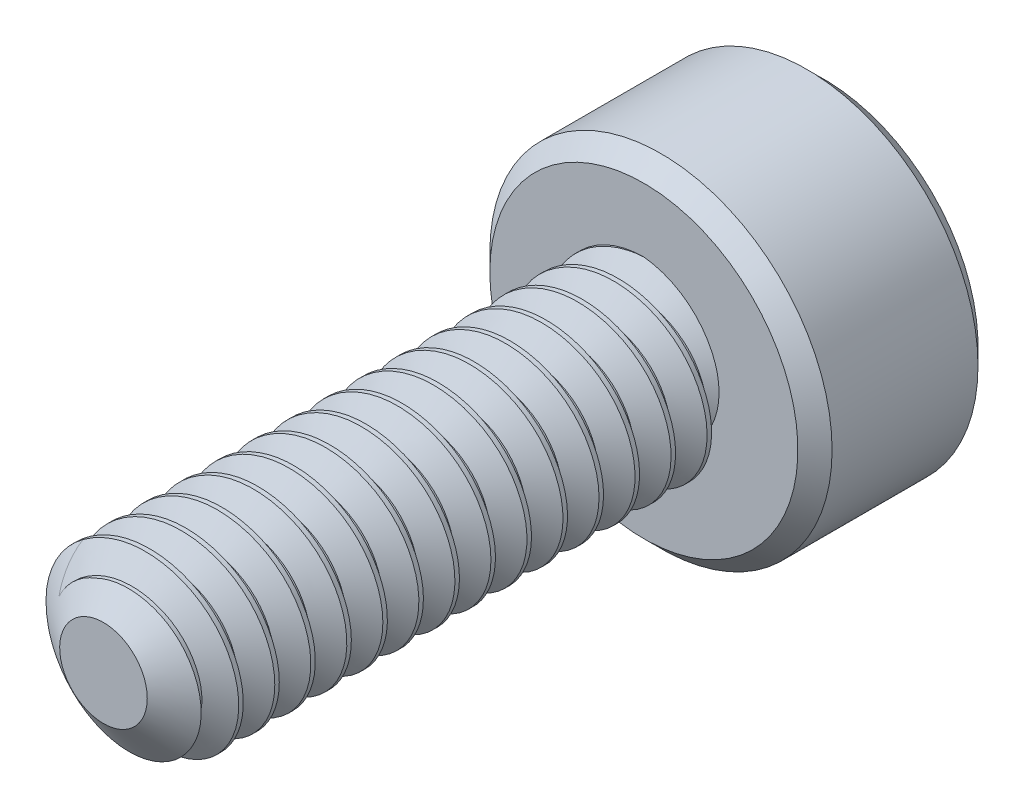
SolidWorks part; units mm, degrees
other "DetailItem1"
material "Plain Carbon Steel"
ref_plane "Front Plane" through (0, 0, 0) normal (0, 0, 1) x (1, 0, 0)
ref_plane "Top Plane" through (0, 0, 0) normal (0, 1, 0) x (1, 0, 0)
ref_plane "Right Plane" through (0, 0, 0) normal (1, 0, 0) x (0, 0, -1)
sketch "Sketch1" plane through (0, 0, 0) normal (0, 0, 1) x (1, 0, 0)
  circle A0 centre (0, 0) radius 1
  dimension "OD" = 2
extrude "Extrude1" add sketch "Sketch1" against normal blind 6
sketch "Sketch2" plane through (0, 0, 0) normal (0, 0, 1) x (1, 0, 0)
  circle A0 centre (0, 0) radius 1 construction
  circle A1 centre (0, 0) radius 1
curve "Helix/Spiral1" pitch 0.4 height 6.4 radius 1 centre (0, 0, 0) axis (0, 0, -1) start towards (0, 1, 0) parameters "pitch"=0.4
sketch "Sketch3" plane through (0, 0, 0) normal (1, 0, 0) x (0, 0, -1)
  line L0 (-0.35, 1) -> (-0.2, 0.7402)
  line L1 (-0.2, 0.7402) -> (-0.15, 0.7402)
  line L2 (-0.15, 0.7402) -> (0, 1)
  line L3 (-0.35, 1) -> (0, 1)
  line L4 (-0.175, 1) -> (-0.175, 0.7402) construction
  line L5 (-0.275, 0.8701) -> (-0.075, 0.8701) construction
  line L6 (0, 1) -> (0, -1) construction
  dimension "D1" = 0.05
  dimension "D2" = 0.2
  dimension "D3" = 60
sweep "Cut-Sweep1" cut profiles "Sketch3" path "Helix/Spiral1" align with end faces yes
sketch "Sketch4" plane through (0, 0, 0) normal (1, 0, 0) x (0, 0, -1)
  line L0 (0.3598, 1) -> (0, 0.4862)
  line L1 (0, 0.4862) -> (0, 1)
  line L2 (0.3598, 1) -> (0, 1)
  line L3 (-0.35, 1) -> (0, 1) construction
  line L4 (0, 0) -> (7.0209, 0) construction
  dimension "D1" = 55
  dimension "D2" = 0.254
revolve "Cut-Revolve1" cut sketch "Sketch4" angle 360 about L4
sketch "Sketch6" plane through (0, 0, -6) normal (0, 0, -1) x (-1, 0, 0)
  circle A0 centre (0, 0) radius 1.9
  dimension "head dia" = 3.8
extrude "Extrude2" add sketch "Sketch6" along normal blind 2
sketch "Sketch7" plane through (0, 0, -8) normal (0, 0, -1) x (-1, 0, 0)
  line L1 (0, 0.866) -> (-0.75, 0.433)
  line L2 (-0.75, 0.433) -> (-0.75, -0.433)
  line L3 (-0.75, -0.433) -> (0, -0.866)
  line L4 (0, -0.866) -> (0.75, -0.433)
  line L5 (0.75, -0.433) -> (0.75, 0.433)
  line L6 (0.75, 0.433) -> (0, 0.866)
  circle A0 centre (0, 0) radius 0.75 construction
  dimension "hex dia" = 1.5
extrude "Cut-Extrude1" cut sketch "Sketch7" against normal blind 1.125
sketch "Sketch8" plane through (0, 0, -8) normal (0, 0, -1) x (-1, 0, 0)
  circle A0 centre (0, 0) radius 0.866
extrude "Cut-Extrude2" cut sketch "Sketch8" against normal through all draft 45
chamfer "Chamfer1" distance 0.19 angle 45 2 edges at (-1.9, 0, -8) (-1.9, 0, -6)
sketch "Sketch10" plane through (0, 0, -6) normal (0, 0, 1) x (1, 0, 0)
  circle A1 centre (0, 0) radius 1
  circle A2 centre (0, 0) radius 1
  dimension "D1" = 0
ref_plane "Plane1" through (0, 0, 0) normal (0, 0, 1) x (1, 0, 0)
extrude "partial thread" [suppressed] add sketch "Sketch10" along normal up to surface (36 mm away) separate body up to plane "Plane1"
chamfer "Chamfer2" [suppressed] distance 0.04 angle 45
combine bodies "Combine1" [suppressed] operation type add bodies to combine 107 108
sketch "Sketch9" plane through (0, 0, 0) normal (1, 0, 0) x (0, 0, -1)
  line L0 (0, 1) -> (0, -1) construction
  line L1 (1, 1) -> (1, -1) construction
  dimension "D1" = 1
equation "\"D3@Helix/Spiral1\" = \"screw length@Extrude1\"+\"pitch@Helix/Spiral1\""
equation "\"D1@Sketch3\" = \"pitch@Helix/Spiral1\"*.125"
equation "\"D2@Sketch3\" = \"pitch@Helix/Spiral1\"*.5"
equation "\"D1@Cut-Extrude1\" = \"hex dia@Sketch7\"*.75"
equation "\"D1@Chamfer1\" = \"head dia@Sketch6\"*.05"
equation "\"D1@Sketch9\" = \"pitch@Helix/Spiral1\"*2.5"
equation "\"D1@Chamfer2\"=\"OD@Sketch1\"*.02"
